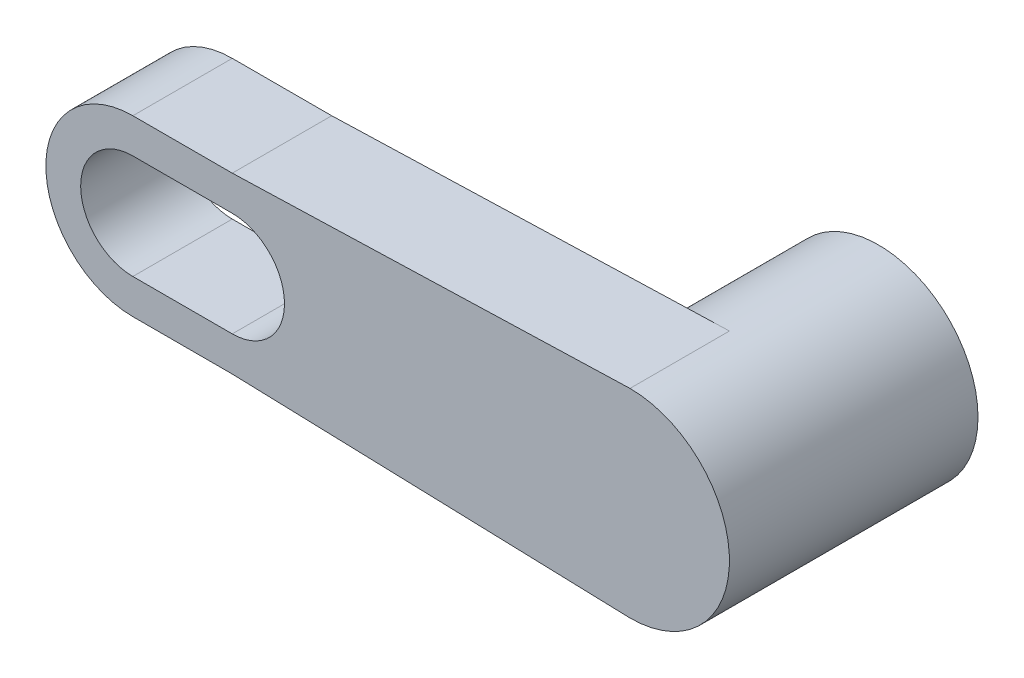
SolidWorks part; units mm, degrees
material "ABS"
ref_plane "Plan de face" through (0, 0, 0) normal (0, 0, 1) x (1, 0, 0)
ref_plane "Plan de dessus" through (0, 0, 0) normal (0, 1, 0) x (1, 0, 0)
ref_plane "Plan de droite" through (0, 0, 0) normal (1, 0, 0) x (0, 0, -1)
sketch "Esquisse1" plane through (0, 0, 0) normal (0, 0, 1) x (1, 0, 0)
  line L0 (-2, 0) -> (2, 0) construction
  line L1 (-2, 2.1) -> (2, 2.1)
  line L2 (-2, -2.1) -> (2, -2.1)
  line L3 (2, 0) -> (-2, 0) construction
  line L4 (2, -3.5) -> (-2, -3.5)
  line L5 (2, 3.5) -> (-2, 3.5)
  line L9 (2, 3.5) -> (2, 2.1) construction
  line L10 (2, -2.1) -> (2, -3.5) construction
  line L11 (-2, 2.1) -> (-2, 3.5) construction
  line L12 (-2, -2.1) -> (-2, -3.5) construction
  line L13 (-2, 0) -> (0, 0) construction
  line L14 (0, 0) -> (18, 0) construction
  line L15 (18, -4) -> (18, 4) construction
  line L16 (2, 3.5) -> (18, 4)
  line L17 (18, -4) -> (2, -3.5)
  arc A0 (-2, 2.1) -> (-2, -2.1) centre (-2, 0) ccw
  arc A1 (2, -2.1) -> (2, 2.1) centre (2, 0) ccw
  arc A3 (-2, 3.5) -> (-2, -3.5) centre (-2, 0) ccw
  circle A4 centre (18, 0) radius 2.5 construction
  arc A6 (18, -4) -> (18, 4) centre (18, 0) ccw
  point P2 (0, 0)
  point P10 (0, 0)
  point P19 (2, 3.5)
  dimension "D1" = 2.1
  dimension "D3" = 3.5
  dimension "D8" = 5
  dimension "D5" = 1.5
  dimension "D2" = 2
  dimension "D6" = 2
  dimension "D7" = 18
extrude "Boss.-Extru.1" add sketch "Esquisse1" along normal blind 4
sketch "Esquisse2" plane through (0, 0, 0) normal (0, 0, 1) x (1, 0, 0)
  circle A0 centre (18, 0) radius 4
extrude "Boss.-Extru.2" add sketch "Esquisse2" against normal blind 6
sketch "Esquisse3" plane through (0, 0, 0) normal (0, 0, 1) x (1, 0, 0)
  circle A0 centre (18, 0) radius 2.5
  dimension "D1" = 5
extrude "Enlèv. mat.-Extru.1" cut sketch "Esquisse3" along normal blind 5 from surface starting at face at (22, 0, -6)
